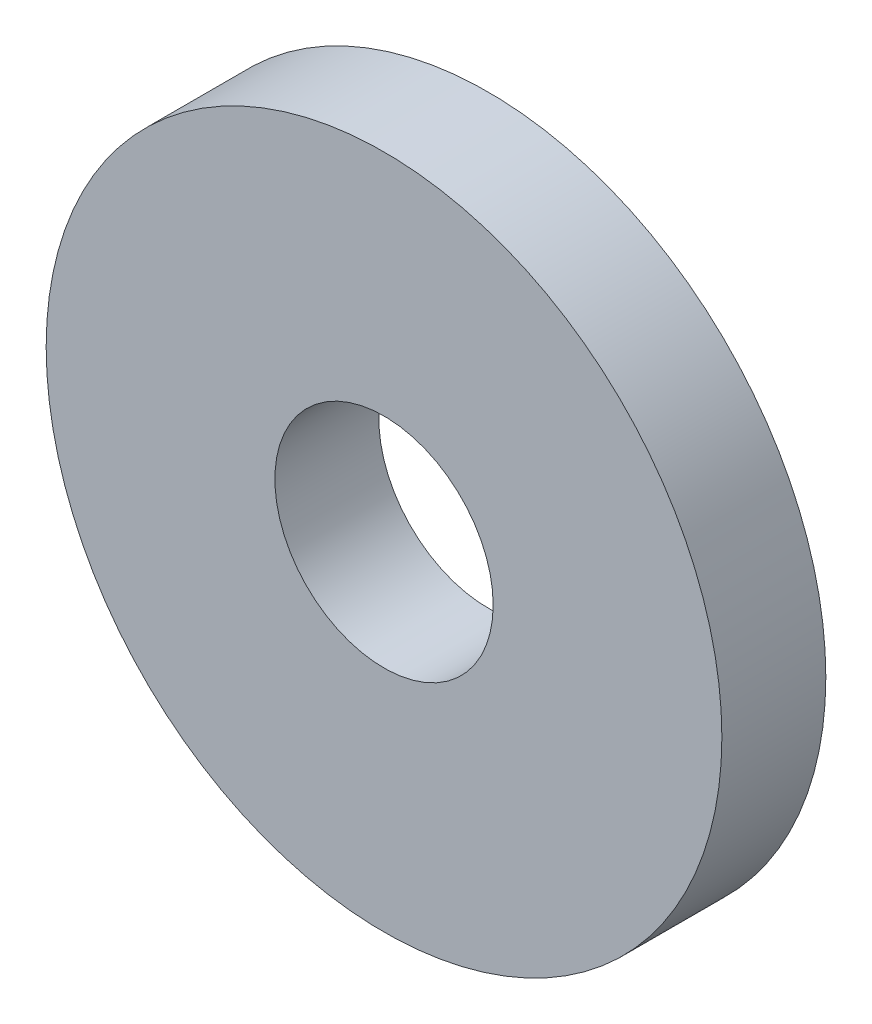
SolidWorks part; units mm, degrees
ref_plane "Front Plane" through (0, 0, 0) normal (0, 0, 1) x (1, 0, 0)
ref_plane "Top Plane" through (0, 0, 0) normal (0, 1, 0) x (1, 0, 0)
ref_plane "Right Plane" through (0, 0, 0) normal (1, 0, 0) x (0, 0, -1)
sketch "Sketch1" plane through (0, 0, 0) normal (0, 0, 1) x (1, 0, 0)
  circle A0 centre (0, 0) radius 6.5
  circle A1 centre (0, 0) radius 2.1
  dimension "OD" = 13
  dimension "ID" = 4.2
extrude "Extrude1" add sketch "Sketch1" along normal mid plane 2
sketch "Sketch2" plane through (0, 0, 0) normal (1, 0, 0) x (0, 0, -1)
  line L0 (-1, -2.1) -> (1, -2.1) construction
  line L3 (1, 2.1) -> (-1, 2.1) construction
  line L5 (-1, -2.1) -> (1, -2.1)
  line L6 (1, 2.1) -> (-1, 2.1)
sketch "Sketch4" plane through (0, 0, 1) normal (0, 0, 1) x (1, 0, 0)
  line L0 (0, 0) -> (-1.4849, 1.4849)
  line L1 (0, -7.15) -> (0, 7.15) construction
  circle A0 centre (0, 0) radius 2.1 construction
  dimension "D1" = 45
